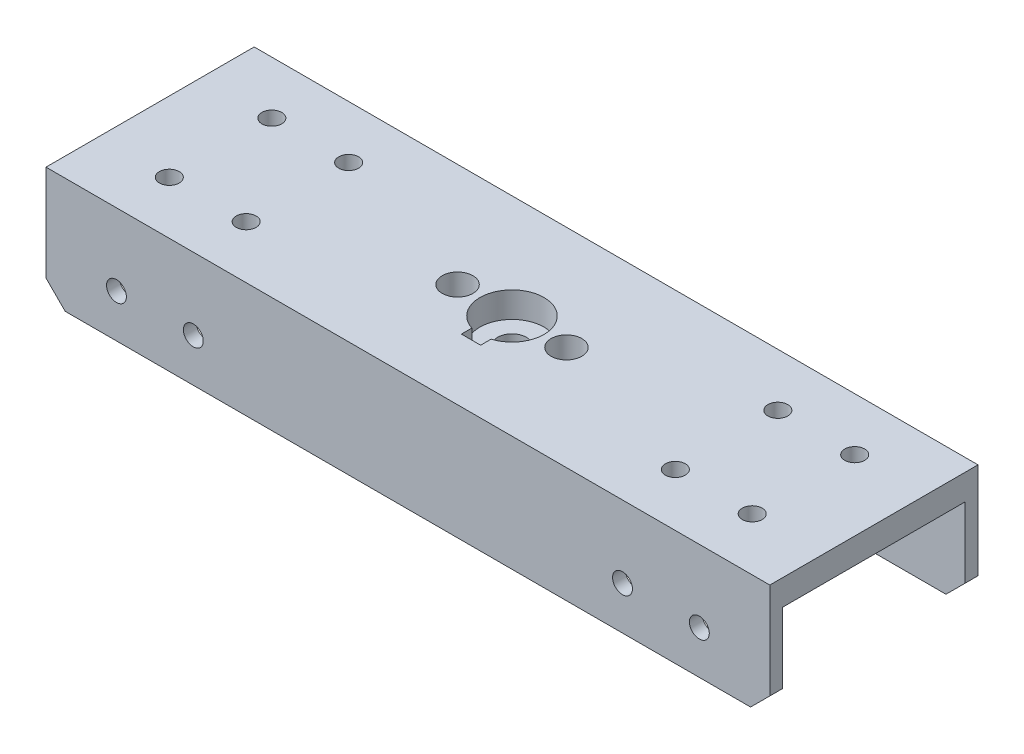
SolidWorks part; units mm, degrees
material "6061-T6 (SS)"
ref_plane "Front Plane" through (0, 0, 0) normal (0, 0, 1) x (1, 0, 0)
ref_plane "Top Plane" through (0, 0, 0) normal (0, 1, 0) x (1, 0, 0)
ref_plane "Right Plane" through (0, 0, 0) normal (1, 0, 0) x (0, 0, -1)
sketch "Sketch1" plane through (0, 0, 0) normal (0, 1, 0) x (1, 0, 0)
  line L1 (0, 0) -> (113, 0)
  line L2 (0, 0) -> (0, 32.5)
  line L3 (0, 32.5) -> (113, 32.5)
  line L4 (113, 0) -> (113, 32.5)
  dimension "D1" = 32.5
  dimension "D2" = 113
extrude "Boss-Extrude1" add sketch "Sketch1" along normal blind 4
sketch "Sketch4" plane through (0, 4, 0) normal (0, 1, 0) x (1, 0, 0)
  line L0 (56.5, 32.5) -> (56.5, -12.4802) construction
  line L1 (113, 32.5) -> (0, 32.5) construction
  line L3 (0, 16.25) -> (122.1673, 16.25) construction
  line L4 (0, 32.5) -> (0, 0) construction
  point P0 (11, 24.25)
  point P12 (23, 24.25)
  point P13 (23, 8.25)
  point P14 (11, 8.25)
  point P25 (102, 8.25)
  point P26 (90, 8.25)
  point P27 (90, 24.25)
  point P28 (102, 24.25)
  dimension "D1" = 2
  dimension "D3" = 12
  dimension "D4" = 16
  dimension "D5" = 8
  dimension "D6" = 79
  dimension "D2" = 2
hole_wizard "M2.5 Clearance Hole2" positions "Sketch4" profile "Sketch3" hole size "M2.5" standard "DIN" end condition through all
sketch "Sketch3" plane through (11, 4, -24.25) normal (1, 0, 0) x (0, 0, 1)
  line L0 (0, 0) -> (0, 4)
  line L1 (0, 4) -> (1.55, 4)
  line L2 (1.55, 4) -> (1.55, 0)
  line L5 (1.55, 0) -> (0, 0)
  line L11 (0, -6.35) -> (0, 107.95) construction
  dimension "Thru Hole Dia." = 3.1
  dimension "Thru Hole Depth" = 4
sketch "Sketch5" plane through (0, 0, 0) normal (0, -1, 0) x (1, 0, 0)
  line L0 (0, -16.25) -> (113, -16.25) construction
  line L1 (0, 0) -> (113, 0)
  line L3 (0, -32.5) -> (113, -32.5)
  line L5 (0, -2) -> (113, -2)
  line L7 (0, -30.5) -> (113, -30.5)
  line L9 (0, -16.25) -> (113, -16.25) construction
  line L20 (0, 0) -> (0, -2)
  line L23 (0, -32.5) -> (0, -30.5)
  line L24 (113, 0) -> (113, -2)
  line L25 (113, -30.5) -> (113, -32.5)
  line L26 (113, 0) -> (113, -32.5) construction
  line L27 (0, -32.5) -> (0, 0) construction
  dimension "D1" = 28.5
  dimension "D2" = 180
extrude "Boss-Extrude2" add sketch "Sketch5" along normal blind 14
sketch "Sketch7" plane through (0, -14, 0) normal (0, -1, 0) x (1, 0, 0)
  line L1 (0, -2) -> (113, -2) construction
  line L2 (34.5, -2) -> (78.5, -2)
  line L3 (34.5, -2) -> (34.5, -30.5)
  line L5 (113, -30.5) -> (0, -30.5) construction
  line L6 (34.5, -30.5) -> (78.5, -30.5)
  line L21 (78.5, -2) -> (78.5, -30.5)
  line L22 (113, -30.5) -> (0, -30.5) construction
  point P10 (56.5, -30.5)
  dimension "D1" = 44
extrude "Boss-Extrude3" add sketch "Sketch7" against normal up to next
sketch "Sketch10" plane through (0, 0, -32.5) normal (0, 0, -1) x (-1, 0, 0)
  line L1 (0, 0) -> (-34.5, 0) construction
  line L2 (-23, -7.25) -> (-11, -7.25)
  line L4 (-9.55, 1.1) -> (-12.45, 1.1)
  line L5 (-11, 1.1) -> (-11, -7.25)
  line L8 (-56.5, 4) -> (-56.5, -40.6573) construction
  line L9 (-113, 4) -> (0, 4) construction
  point P0 (-11, -7.25)
  point P2 (-23, -7.25)
  point P30 (-102, -7.25)
  point P31 (-90, -7.25)
  dimension "D1" = 7.25
  dimension "D2" = 12
hole_wizard "M2.5 Clearance Hole1" positions "Sketch10" profile "Sketch9" hole size "M2.5" standard "DIN" end condition through all
sketch "Sketch9" plane through (11, -7.25, -32.5) normal (1, 0, 0) x (0, 1, 0)
  line L0 (0, 0) -> (0, 32.5)
  line L1 (0, 32.5) -> (1.55, 32.5)
  line L2 (1.55, 32.5) -> (1.55, 0)
  line L5 (1.55, 0) -> (0, 0)
  line L11 (0, -6.35) -> (0, 107.95) construction
  dimension "Thru Hole Dia." = 3.1
  dimension "Thru Hole Depth" = 32.5
sketch "Sketch11" plane through (0, -14, 0) normal (0, -1, 0) x (1, 0, 0)
  line L24 (38.5, -4) -> (38.5, -28.5)
  line L25 (38.5, -28.5) -> (74.5, -28.5)
  line L26 (74.5, -28.5) -> (74.5, -4)
  line L27 (74.5, -4) -> (38.5, -4)
  line L28 (38.5, -4) -> (38.5, -28.5)
  line L29 (38.5, -28.5) -> (74.5, -28.5)
  line L30 (74.5, -28.5) -> (74.5, -4)
  line L31 (74.5, -4) -> (38.5, -4)
  dimension "D1" = 4
extrude "Cut-Extrude1" cut sketch "Sketch11" against normal blind 14
sketch "Sketch14" plane through (0, 4, 0) normal (0, 1, 0) x (1, 0, 0)
  line L0 (0, 32.5) -> (113, 0)
  line L1 (113, 0) -> (113, 32.5)
  line L2 (113, 32.5) -> (0, 0)
  point P12 (56.5, 16.25)
hole_wizard "Ø10.0mm Dowel Hole1" positions "Sketch14" profile "Sketch13" hole size "Ø10.0" standard "DIN" end condition through all
sketch "Sketch13" plane through (56.5, 4, -16.25) normal (1, 0, 0) x (0, 0, 1)
  line L0 (0, 0) -> (0, 18)
  line L1 (0, 18) -> (5, 18)
  line L2 (5, 18) -> (5, 0)
  line L5 (5, 0) -> (0, 0)
  line L11 (0, -6.35) -> (0, 107.95) construction
  dimension "Thru Hole Dia." = 10
  dimension "Thru Hole Depth" = 18
fillet "Fillet1" radius 4 4 edges at (38.5, -7, -28.5) (38.5, -7, -4) (74.5, -7, -4) (74.5, -7, -28.5)
sketch "Sketch15" plane through (0, -14, 0) normal (0, -1, 0) x (1, 0, 0)
  line L0 (0, -2) -> (34.5, -2) construction
  line L1 (34.5, -2) -> (34.5, -30.5) construction
  line L2 (78.5, -2) -> (78.5, -30.5) construction
  line L3 (34.5, -30.5) -> (0, -30.5) construction
  line L4 (78.5, -2) -> (113, -2) construction
  line L5 (113, -30.5) -> (78.5, -30.5) construction
  circle A0 centre (34.5, -3.6) radius 1.6
  circle A1 centre (34.5, -28.9) radius 1.6
  circle A2 centre (78.5, -3.6) radius 1.6
  circle A3 centre (78.5, -28.9) radius 1.6
  dimension "D1" = 3.2
extrude "Cut-Extrude2" cut sketch "Sketch15" against normal up to surface (14 mm away) and the other way through all up to face at (17.25, 0, -16.25)
fillet "Fillet2" radius 3.2 4 edges at (78.5, -7, -27.3) (78.5, -7, -5.2) (34.5, -7, -27.3) (34.5, -7, -5.2)
chamfer "Chamfer1" distance 3 angle 45 4 edges at (113, -14, -31.5) (113, -14, -1) (0, -14, -31.5) (0, -14, -1)
sketch "Sketch20" plane through (0, 0, 0) normal (0, -1, 0) x (1, 0, 0)
  line L1 (55, -11.4803) -> (58, -11.4803)
  line L2 (55, -11.4803) -> (55, -9.85)
  line L3 (55, -9.85) -> (58, -9.85)
  line L4 (58, -11.4803) -> (58, -9.85)
  circle A0 centre (56.5, -16.25) radius 5 construction
  point P6 (56.5, -11.25)
  dimension "D1" = 1.4
  dimension "D2" = 3
extrude "Cut-Extrude4" cut sketch "Sketch20" against normal through all
sketch "Sketch23" plane through (0, 0, 0) normal (0, -1, 0) x (-1, 0, 0)
  circle A0 centre (-56.5, 16.25) radius 8.5
  point P4 (-65, 16.25)
  point P6 (-48, 16.25)
  dimension "D1" = 17
hole_wizard "M4 Clearance Hole2" positions "Sketch23" profile "Sketch22" hole size "M4" standard "DIN" end condition through all
sketch "Sketch22" plane through (48, 0, -16.25) normal (1, 0, 0) x (0, 0, -1)
  line L0 (0, 0) -> (0, 4)
  line L1 (0, 4) -> (2.4, 4)
  line L2 (2.4, 4) -> (2.4, 0)
  line L5 (2.4, 0) -> (0, 0)
  line L11 (0, -6.35) -> (0, 107.95) construction
  dimension "Thru Hole Dia." = 4.8
  dimension "Thru Hole Depth" = 4
sketch "Sketch24" plane through (0, 0, 0) normal (0, -1, 0) x (1, 0, 0)
  line L8 (39.5, -8) -> (39.5, -24.5)
  line L9 (42.5, -27.5) -> (70.5, -27.5)
  line L10 (73.5, -24.5) -> (73.5, -8)
  line L11 (70.5, -5) -> (42.5, -5)
  line L12 (39.5, -8) -> (39.5, -24.5)
  line L13 (42.5, -27.5) -> (70.5, -27.5)
  line L14 (73.5, -24.5) -> (73.5, -8)
  line L15 (70.5, -5) -> (42.5, -5)
  circle A0 centre (48, -16.25) radius 3.25
  circle A1 centre (65, -16.25) radius 3.25
  arc A10 (39.5, -24.5) -> (42.5, -27.5) centre (42.5, -24.5) ccw
  arc A11 (70.5, -27.5) -> (73.5, -24.5) centre (70.5, -24.5) ccw
  arc A12 (73.5, -8) -> (70.5, -5) centre (70.5, -8) ccw
  arc A13 (42.5, -5) -> (39.5, -8) centre (42.5, -8) ccw
  arc A14 (39.5, -24.5) -> (42.5, -27.5) centre (42.5, -24.5) ccw
  arc A15 (70.5, -27.5) -> (73.5, -24.5) centre (70.5, -24.5) ccw
  arc A16 (73.5, -8) -> (70.5, -5) centre (70.5, -8) ccw
  arc A17 (42.5, -5) -> (39.5, -8) centre (42.5, -8) ccw
  dimension "D1" = 6.5
  dimension "D2" = 1
extrude "Boss-Extrude4" add sketch "Sketch24" along normal blind 10 separate body
sketch "Sketch27" plane through (0, -10, 0) normal (0, -1, 0) x (-1, 0, 0)
  point P0 (-56.5, 16.25)
hole_wizard "M4 Clearance Hole3" positions "Sketch27" profile "Sketch26" hole size "M4" standard "DIN" end condition up to next
sketch "Sketch26" plane through (56.5, -10, -16.25) normal (1, 0, 0) x (0, 0, -1)
  line L0 (0, 0) -> (0, 10.001)
  line L1 (0, 10.001) -> (2.25, 10.001)
  line L2 (2.25, 10.001) -> (2.25, 0)
  line L5 (2.25, 0) -> (0, 0)
  line L11 (0, -6.35) -> (0, 107.95) construction
  dimension "Thru Hole Dia." = 4.5
  dimension "Thru Hole Depth" = 10.001
